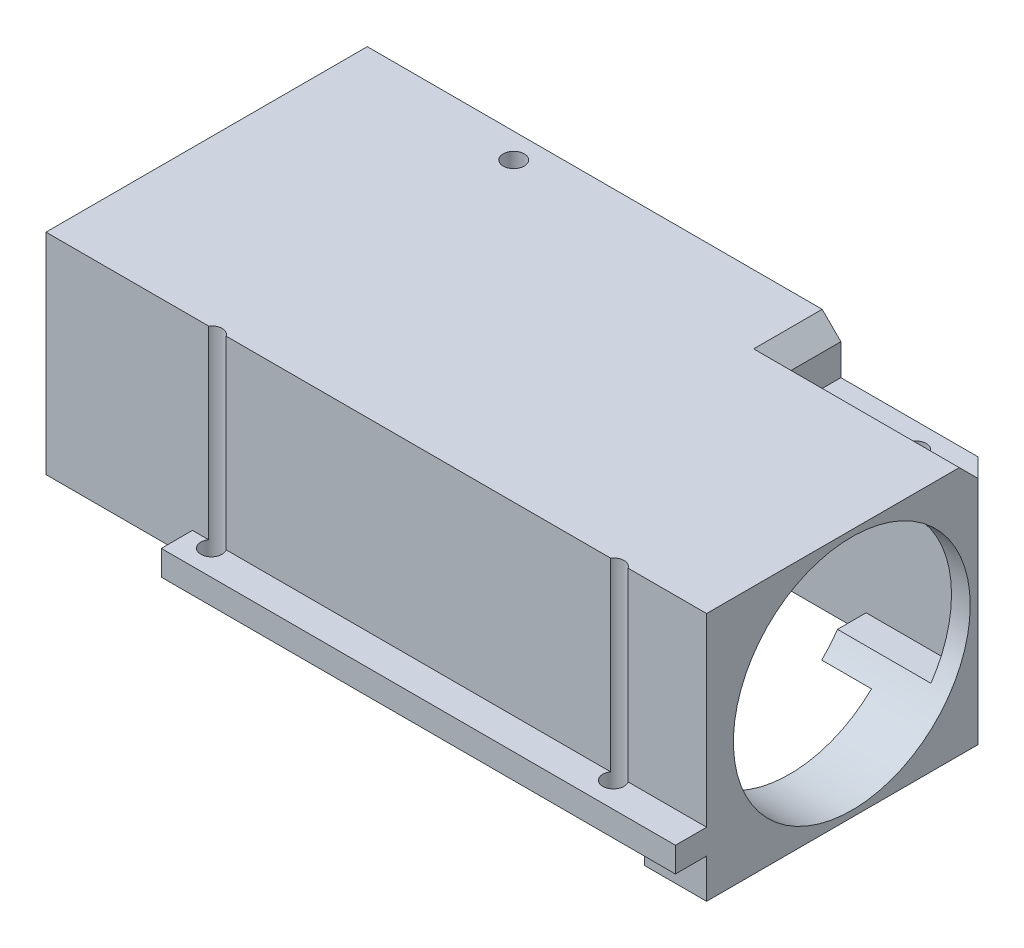
SolidWorks part; units mm, degrees
ref_plane "Front Plane" through (0, 0, 0) normal (0, 0, 1) x (1, 0, 0)
ref_plane "Top Plane" through (0, 0, 0) normal (0, 1, 0) x (1, 0, 0)
ref_plane "Right Plane" through (0, 0, 0) normal (1, 0, 0) x (0, 0, -1)
sketch "Sketch1" plane through (0, 0, 0) normal (0, 0, 1) x (1, 0, 0)
  line L0 (0, 0) -> (0, 40)
  line L1 (0, 40) -> (-106, 40)
  line L2 (-106, 40) -> (-106, 35)
  line L3 (-106, 35) -> (-3, 35)
  line L6 (0, 0) -> (-10, 0)
  line L7 (-10, 0) -> (-10, 6.3)
  line L8 (-10, 6.3) -> (-18, 6.3)
  line L9 (-18, 6.3) -> (-18, 9.3)
  line L10 (-3, 35) -> (-3, 9.3)
  line L11 (-3, 9.3) -> (-18, 9.3)
  dimension "D1" = 40
  dimension "D2" = 106
  dimension "D3" = 5
  dimension "D4" = 10
  dimension "D5" = 6.3
  dimension "D6" = 3
  dimension "D7" = 3
  dimension "D8" = 8
extrude "Boss-Extrude1" add sketch "Sketch1" along normal blind 46.6
sketch "Sketch2" plane through (0, 0, 0) normal (1, 0, 0) x (0, 0, -1)
  line L0 (0, 0) -> (0, 40) construction
  line L1 (-46.6, 0) -> (0, 0) construction
  circle A0 centre (-23.3, 20) radius 19
  dimension "D1" = 38
  dimension "D2" = 23.3
  dimension "D3" = 20
extrude "Cut-Extrude1" cut sketch "Sketch2" against normal up to next
sketch "Sketch3" plane through (-3, 0, 0) normal (-1, 0, 0) x (0, 0, 1)
  line L0 (46.6, 35) -> (34.9619, 35) construction
  line L1 (46.6, 6.3) -> (43.6, 6.3)
  line L2 (46.6, 6.3) -> (46.6, 35)
  line L3 (46.6, 35) -> (43.6, 35)
  line L4 (43.6, 6.3) -> (43.6, 35)
  dimension "D1" = 3
extrude "Boss-Extrude2" add sketch "Sketch3" along normal blind 103
sketch "Sketch4" plane through (0, 0, 0) normal (1, 0, 0) x (0, 0, -1)
  line L0 (-46.6, 0) -> (-46.6, 40) construction
  line L1 (-46.6, 6.3) -> (-51.6, 6.3)
  line L2 (-46.6, 6.3) -> (-46.6, 10.3)
  line L3 (-46.6, 10.3) -> (-51.6, 10.3)
  line L4 (-51.6, 6.3) -> (-51.6, 10.3)
  dimension "D1" = 0
  dimension "D2" = 4
  dimension "D3" = 5
extrude "Boss-Extrude3" add sketch "Sketch4" against normal blind 82.5
sketch "Sketch6" plane through (0, 0, 0) normal (1, 0, 0) x (0, 0, -1)
  line L1 (0, 40) -> (-3, 40)
  line L2 (0, 40) -> (0, 6.3)
  line L3 (0, 6.3) -> (-3, 6.3)
  line L4 (-3, 40) -> (-3, 6.3)
  dimension "D1" = 0
  dimension "D2" = 3
extrude "Boss-Extrude4" add sketch "Sketch6" against normal blind 106
sketch "Sketch8" plane through (0, 0, 0) normal (1, 0, 0) x (0, 0, -1)
  line L5 (0, 40) -> (4.95, 40)
  line L6 (0, 40) -> (0, 6.3)
  line L7 (0, 6.3) -> (4.95, 6.3)
  line L8 (4.95, 40) -> (4.95, 6.3)
  dimension "D1" = 4.95
  dimension "D2" = 6.3
extrude "Boss-Extrude5" add sketch "Sketch8" against normal blind 106
chamfer "Chamfer2" distance 8 angle 45 1 edges at (0, 23.15, -4.95)
hole_wizard "M3 Clearance Hole1" positions "3DSketch1" profile "Sketch10" hole size "M3" standard "ISO" end condition through all
sketch3d "3DSketch1"
  line L0 (-14, 6.3, -0.95) -> (-14, 0, -0.95) construction
  line L1 (-14, 6.3, 47.55) -> (-14, 0, 47.55) construction
  line L2 (-78.5, 6.3, 47.55) -> (-78.5, 0, 47.55) construction
  line L3 (-78.5, -3, -0.95) -> (-78.5, 0, -0.95) construction
  point P0 (-14, 0, -0.95)
  point P4 (-14, 0, 47.55)
  point P8 (-78.5, 0, 47.55)
  point P12 (-78.5, -3, -0.95)
sketch "Sketch10" plane through (-14, 0, -0.95) normal (1, 0, 0) x (0, 0, -1)
  line L0 (0, 0) -> (0, 40)
  line L1 (0, 40) -> (1.7, 40)
  line L2 (1.7, 40) -> (1.7, 0)
  line L5 (1.7, 0) -> (0, 0)
  line L11 (0, -6.35) -> (0, 107.95) construction
  dimension "Thru Hole Dia." = 3.4
  dimension "Thru Hole Depth" = 40
chamfer "Chamfer3" distance 6 angle 45 2 edges at (-54.5, 35, 43.6) (-54.5, 35, 3)
sketch "Sketch12" plane through (0, 0, 0) normal (1, 0, 0) x (0, 0, -1)
  line L1 (4.95, 40) -> (-3.05, 40)
  line L2 (4.95, 40) -> (4.95, 32)
  line L3 (4.95, 32) -> (-3.05, 32)
  line L4 (-3.05, 40) -> (-3.05, 32)
  dimension "D1" = 8
  dimension "D2" = 8
extrude "Cut-Extrude4" cut sketch "Sketch12" against normal blind 30
chamfer "Chamfer4" distance 3 angle 45 2 edges at (-30, 40, -0.95) (-15, 40, 3.05)
